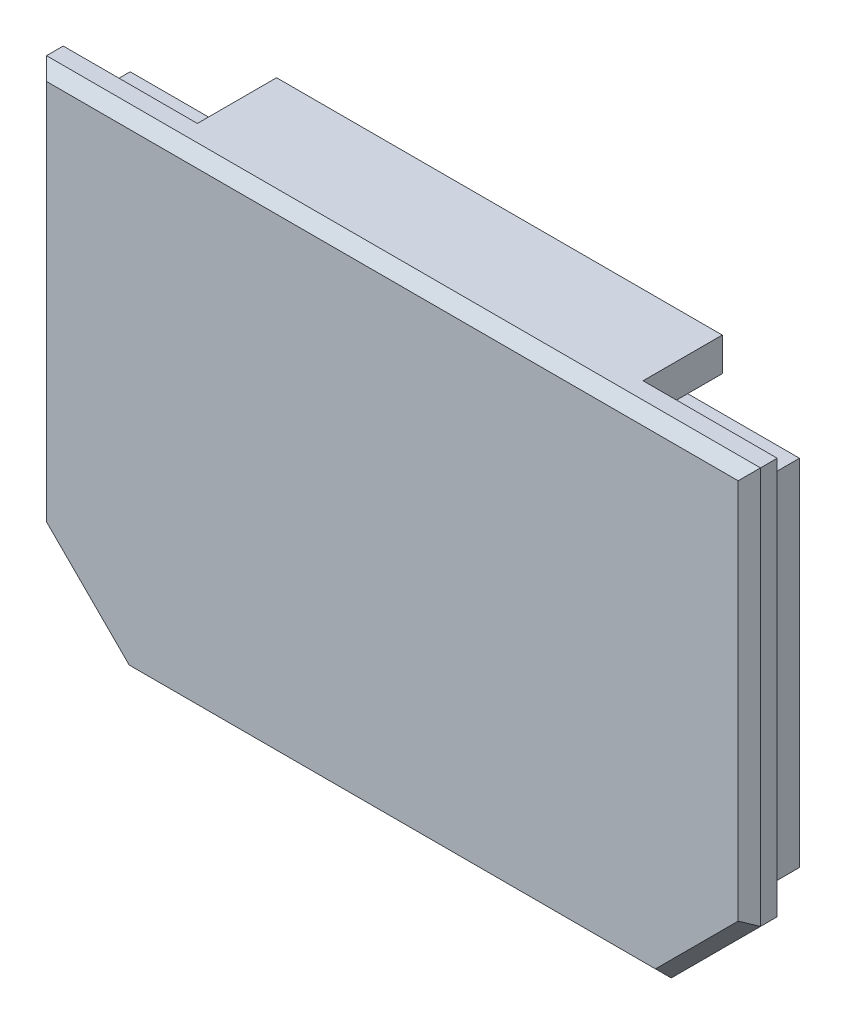
SolidWorks part; units mm, degrees
ref_plane "Front Plane" through (0, 0, 0) normal (0, 0, 1) x (1, 0, 0)
ref_plane "Top Plane" through (0, 0, 0) normal (0, 1, 0) x (1, 0, 0)
ref_plane "Right Plane" through (0, 0, 0) normal (1, 0, 0) x (0, 0, -1)
sketch "Sketch1" plane through (0, 0, 0) normal (0, 0, 1) x (1, 0, 0)
  line L32 (-20, -3) -> (-20, 0)
  line L33 (-20, 0) -> (-32, 0)
  line L34 (-32, 0) -> (-32, -35.6)
  line L35 (-32, -35.6) -> (-24, -43.6)
  line L36 (-24, -43.6) -> (24, -43.6)
  line L37 (24, -43.6) -> (32, -35.6)
  line L38 (32, -35.6) -> (32, 0)
  line L39 (32, 0) -> (20, 0)
  line L40 (20, 0) -> (20, -3)
  line L41 (20, -3) -> (30, -3)
  line L42 (30, -3) -> (30, -34.7716)
  line L43 (30, -34.7716) -> (23.1716, -41.6)
  line L44 (23.1716, -41.6) -> (-23.1716, -41.6)
  line L45 (-23.1716, -41.6) -> (-30, -34.7716)
  line L46 (-30, -34.7716) -> (-30, -3)
  line L47 (-30, -3) -> (-20, -3)
sketch "Sketch2" plane through (0, 0, 0) normal (0, 0, 1) x (1, 0, 0)
  line L0 (-30, -3) -> (30, -3) construction
  line L1 (30, -3) -> (30, -34.7716) construction
  line L2 (30, -34.7716) -> (23.1716, -41.6) construction
  line L3 (23.1716, -41.6) -> (-23.1716, -41.6) construction
  line L4 (-23.1716, -41.6) -> (-30, -34.7716) construction
  line L5 (-30, -34.7716) -> (-30, -3) construction
  line L6 (-28, -33.9431) -> (-28, -5)
  line L7 (-28, -5) -> (28, -5)
  line L8 (28, -5) -> (28, -33.9431)
  line L9 (28, -33.9431) -> (22.3431, -39.6)
  line L10 (22.3431, -39.6) -> (-22.3431, -39.6)
  line L11 (-22.3431, -39.6) -> (-28, -33.9431)
  line L12 (-29.9999, -3.0001) -> (29.9999, -3.0001)
  line L13 (29.9999, -3.0001) -> (29.9999, -34.7715)
  line L14 (29.9999, -34.7715) -> (23.1715, -41.5999)
  line L15 (23.1715, -41.5999) -> (-23.1715, -41.5999)
  line L16 (-23.1715, -41.5999) -> (-29.9999, -34.7715)
  line L17 (-29.9999, -34.7715) -> (-29.9999, -3.0001)
  dimension "D1" = 2
  dimension "D2" = 0.0001
extrude "Boss-Extrude1" add sketch "Sketch2" against normal blind 4
sketch "Sketch3" plane through (0, 0, 0) normal (0, 0, 1) x (1, 0, 0)
  line L0 (-32, 0) -> (32, 0)
  line L1 (32, 0) -> (32, -35.6)
  line L2 (32, -35.6) -> (24, -43.6)
  line L3 (24, -43.6) -> (-24, -43.6)
  line L4 (-24, -43.6) -> (-32, -35.6)
  line L5 (-32, -35.6) -> (-32, 0)
extrude "Boss-Extrude2" add sketch "Sketch3" along normal blind 2.5
chamfer "Chamfer1" distance 1 angle 45 6 edges at (0, 0, 2.5) (32, -17.8, 2.5) (28, -39.6, 2.5) (0, -43.6, 2.5) (-28, -39.6, 2.5) (-32, -17.8, 2.5)
sketch "Sketch4" plane through (0, -43.6, 0) normal (0, -1, 0) x (1, 0, 0)
  line L1 (-3, -0.75) -> (3, -0.75)
  line L2 (-3, -0.75) -> (-3, 0.75)
  line L3 (-3, 0.75) -> (3, 0.75)
  line L4 (3, -0.75) -> (3, 0.75)
  line L5 (-3, -0.75) -> (3, 0.75) construction
  line L6 (-3, 0.75) -> (3, -0.75) construction
  point P0 (0, 0)
  dimension "D1" = 6
  dimension "D2" = 1.5
extrude "Cut-Extrude1" cut sketch "Sketch4" against normal up to surface (2.0001 mm away) up to face at (0, -41.5999, -2)
chamfer "Chamfer2" distance 1 angle 45 2 edges at (3, -42.5999, 0.75) (-3, -42.5999, 0.75)
sketch "Sketch5" plane through (0, 0, 0) normal (0, 0, -1) x (-1, 0, 0)
  line L0 (-32, 0) -> (32, 0) construction
  line L1 (-19.975, 0) -> (19.975, 0)
  line L2 (-19.975, 0) -> (-19.975, -3.0001)
  line L3 (-19.975, -3.0001) -> (19.975, -3.0001)
  line L4 (19.975, 0) -> (19.975, -3.0001)
  line L5 (-29.9999, -3.0001) -> (29.9999, -3.0001) construction
  line L6 (-20, 0) -> (-20, -3) construction
  line L7 (20, -3) -> (20, 0) construction
  dimension "D1" = 0.025
  dimension "D2" = 0.025
extrude "Boss-Extrude3" add sketch "Sketch5" along normal blind 7.1
